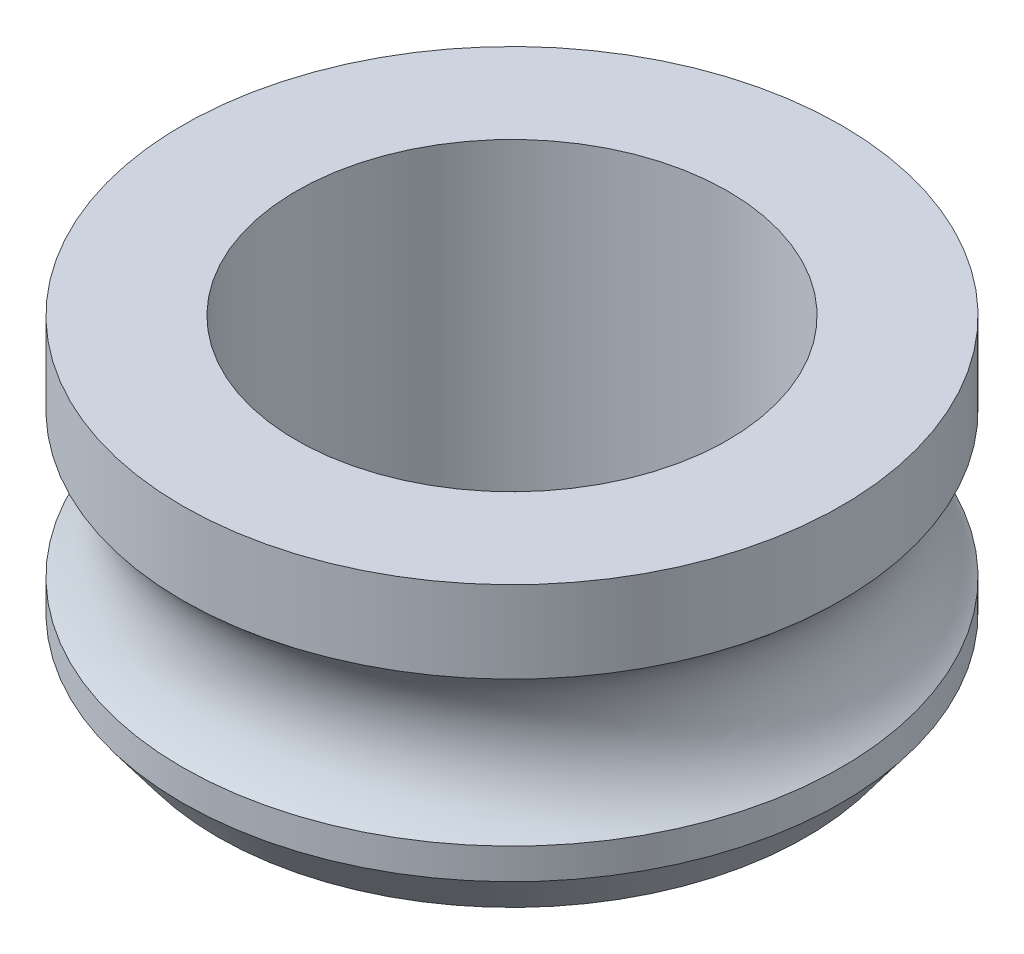
SolidWorks part; units mm, degrees
ref_plane "Front Plane" through (0, 0, 0) normal (0, 0, 1) x (1, 0, 0)
ref_plane "Top Plane" through (0, 0, 0) normal (0, 1, 0) x (1, 0, 0)
ref_plane "Right Plane" through (0, 0, 0) normal (1, 0, 0) x (0, 0, -1)
sketch "Sketch1" plane through (0, 0, 0) normal (0, 1, 0) x (1, 0, 0)
  circle A0 centre (0, 0) radius 27.8
  circle A1 centre (0, 0) radius 18.2
  dimension "D1" = 55.6
  dimension "D2" = 9.6
extrude "Boss-Extrude1" add sketch "Sketch1" along normal blind 25.7
sketch "Sketch2" plane through (0, 0, 0) normal (0, 0, 1) x (1, 0, 0)
  line L0 (27.8, 18.7992) -> (27.8, 6.6008)
  line L1 (27.8, 0) -> (27.8, 25.7) construction
  line L2 (27.8, 12.7) -> (24.8, 12.7)
  line L3 (-27.8, 0) -> (27.8, 0) construction
  line L4 (27.8, 0) -> (27.8, 4)
  line L5 (27.8, 4) -> (24.8, 0)
  line L6 (24.8, 0) -> (27.8, 0)
  arc A0 (27.8, 18.7992) -> (27.8, 6.6008) centre (32.5, 12.7) ccw
  dimension "D2" = 15.4
  dimension "D1" = 3
  dimension "D3" = 12.7
  dimension "D4" = 3
  dimension "D5" = 4
ref_axis "Axis1" through (0, 25.7, 0) along (0, -1, 0)
revolve "Cut-Revolve1" cut sketch "Sketch2" angle 360 about axis through (0, 25.7, 0) along (0, -1, 0) region at (26.5774, 15.0611, 0) region at (26.5774, 10.3389, 0) region at (26.8, 1.3333, 0)
